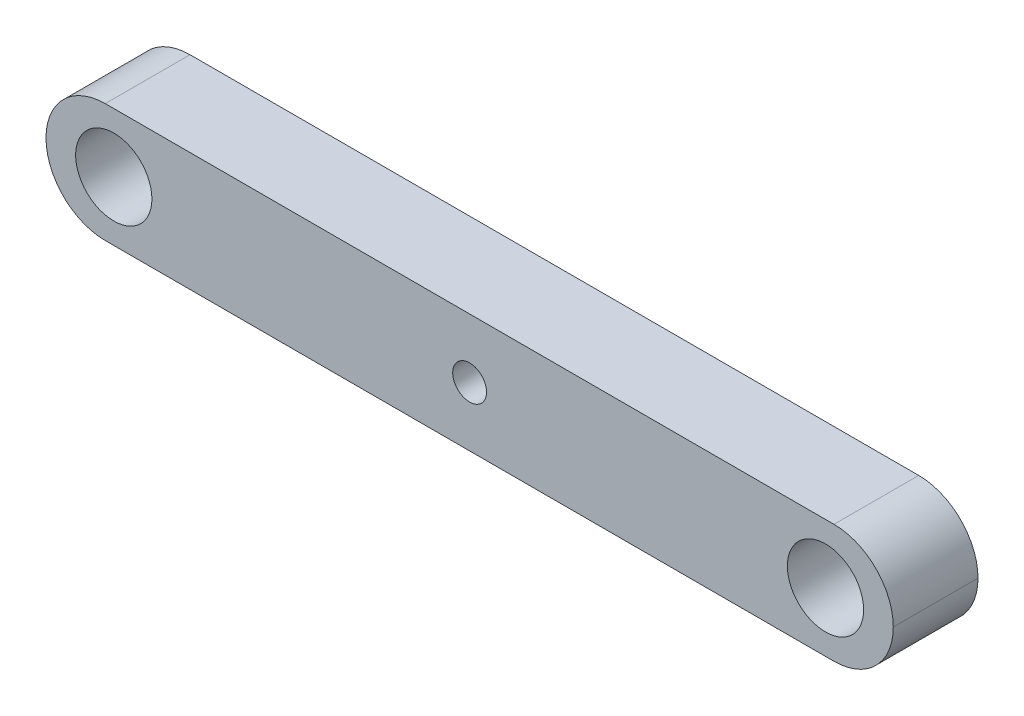
SolidWorks part; units mm, degrees
material "Papel canelado"
ref_plane "Plano frontal" through (0, 0, 0) normal (0, 0, 1) x (1, 0, 0)
ref_plane "Plano superior" through (0, 0, 0) normal (0, 1, 0) x (1, 0, 0)
ref_plane "Plano direito" through (0, 0, 0) normal (1, 0, 0) x (0, 0, -1)
sketch "Esboço1" plane through (0, 0, 0) normal (0, 0, 1) x (1, 0, 0)
  line L0 (-1000, 3.5) -> (49000, 3.5) construction
  line L1 (0, 0) -> (50, 0)
  line L2 (0, 0) -> (0, 7)
  line L3 (0, 7) -> (50, 7)
  line L4 (50, 0) -> (50, 7)
  line L5 (25, -993) -> (25, 49007) construction
  circle A0 centre (25, 3.5) radius 1
  circle A1 centre (4, 3.5) radius 2.25
  circle A2 centre (46, 3.5) radius 2.25
  point P8 (0, 3.5)
  point P11 (25, 7)
  dimension "D3" = 2
  dimension "D4" = 4.5
  dimension "D5" = 4
  dimension "D6" = 4
  dimension "D1" = 7
  dimension "D2" = 50
extrude "Ressalto-extrusão1" add sketch "Esboço1" along normal blind 5
fillet "Filete1" radius 3.5 4 edges at (50, 0, 2.5) (50, 7, 2.5) (0, 0, 2.5) (0, 7, 2.5)
